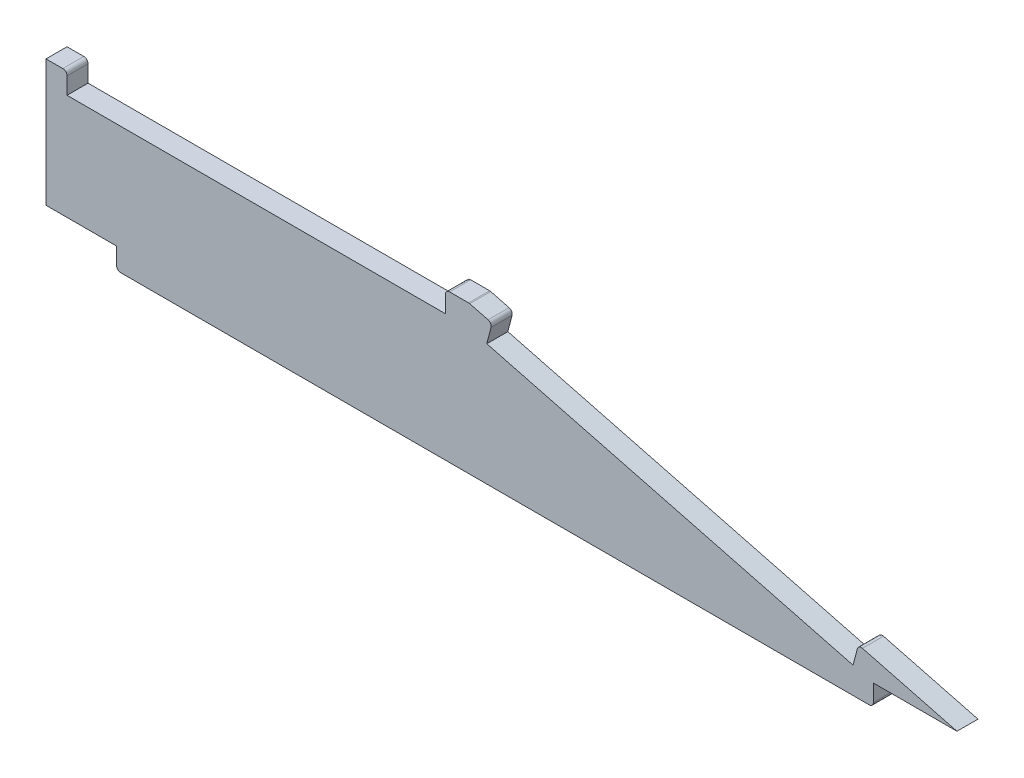
SolidWorks part; units mm, degrees
ref_plane "Front" through (0, 0, 0) normal (0, 0, 1) x (1, 0, 0)
ref_plane "Top" through (0, 0, 0) normal (0, 1, 0) x (1, 0, 0)
ref_plane "Right" through (0, 0, 0) normal (1, 0, 0) x (0, 0, -1)
sketch "Sketch1" plane through (0, 0, 0) normal (0, 0, 1) x (1, 0, 0)
  line L0 (226.1881, 5) -> (227.4461, 9.8391) construction
  line L1 (29.4052, 5) -> (46.1881, 5)
  line L5 (227.4461, 9.8391) -> (222.607, 11.0972) construction
  line L6 (130.6632, 35) -> (129.4052, 30.1609) construction
  line L7 (129.4052, 30.1609) -> (226.1881, 5) construction
  line L8 (134.2443, 28.9028) -> (221.349, 6.258)
  line L9 (134.2443, 28.9028) -> (135.5024, 33.742)
  line L10 (221.349, 6.258) -> (222.607, 11.0972)
  line L12 (222.607, 11.0972) -> (246.0602, 5)
  line L14 (129.4052, 30.1609) -> (29.4052, 30.1609) construction
  line L15 (129.4052, 30.1609) -> (129.4052, 35.1609) construction
  line L16 (129.4052, 35.1609) -> (124.4052, 35.1609) construction
  line L17 (29.4052, 30.1609) -> (29.4052, 35.1609) construction
  line L18 (34.4052, 35.1609) -> (34.4052, 30.1609)
  line L19 (124.4052, 35.1609) -> (124.4052, 30.1609)
  line L20 (34.4052, 30.1609) -> (124.4052, 30.1609)
  line L22 (34.4052, 35.1609) -> (29.4052, 35.1609)
  line L23 (29.4052, 35.1609) -> (29.4052, 5)
  line L25 (46.1881, 5) -> (46.1881, 0)
  line L27 (46.1881, 0) -> (226.1881, 0)
  line L28 (34.4052, 35.1609) -> (29.4052, 35.1609) construction
  line L29 (135.5024, 33.742) -> (130.6632, 35) construction
  line L30 (226.1881, 5) -> (246.0602, 5)
  line L31 (135.5024, 33.742) -> (130.0445, 35.1609)
  line L32 (124.4052, 35.1609) -> (130.0445, 35.1609)
  line L33 (226.1881, 5) -> (226.1881, 0)
  dimension "D1" = 5
  dimension "D2" = 100
  dimension "D3" = 30
  dimension "D4" = 5
  dimension "D5" = 5
  dimension "D6" = 5
  dimension "D7" = 100
  dimension "D8" = 5
  dimension "D9" = 5
  dimension "D10" = 5
  dimension "D11" = 5
  dimension "D12" = 180
extrude "Boss-Extrude1" add sketch "Sketch1" along normal blind 5
fillet "Fillet1" radius 1 7 edges at (226.1881, 0, 2.5) (46.1881, 0, 2.5) (34.4052, 35.1609, 2.5) (124.4052, 35.1609, 2.5) (130.0445, 35.1609, 2.5) (135.5024, 33.742, 2.5) (222.607, 11.0972, 2.5)
